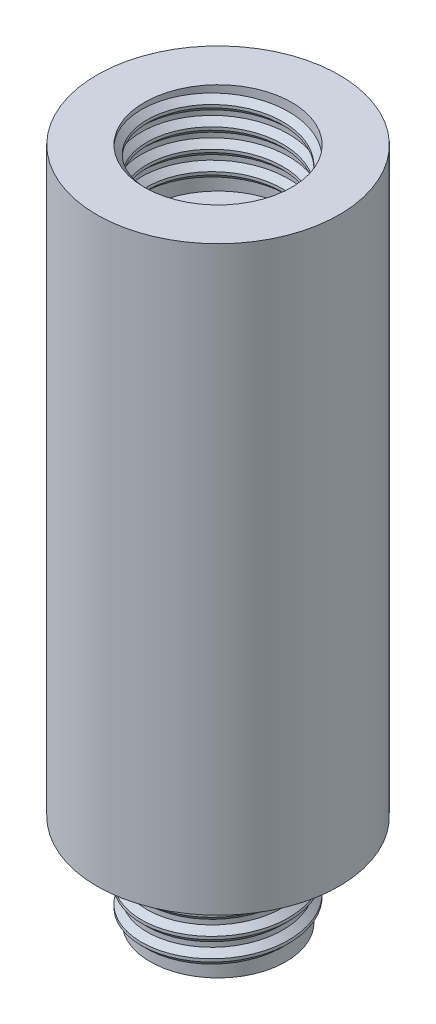
SolidWorks part; units mm, degrees
material "可锻铸铁"
ref_plane "前视基准面" through (0, 0, 0) normal (0, 0, 1) x (1, 0, 0)
ref_plane "上视基准面" through (0, 0, 0) normal (0, 1, 0) x (1, 0, 0)
ref_plane "右视基准面" through (0, 0, 0) normal (1, 0, 0) x (0, 0, -1)
other "Configuration Table"
sketch "草图1" plane through (0, 0, 0) normal (0, 1, 0) x (1, 0, 0)
  circle A0 centre (0, 0) radius 12.5
  dimension "D1" = 25
extrude "凸台-拉伸1" add sketch "草图1" along normal blind 60
sketch "草图14" plane through (0, 60, 0) normal (0, 1, 0) x (1, 0, 0)
  circle A0 centre (0, 0) radius 7.6
  dimension "D1" = 15.2
extrude "切除-拉伸1" cut sketch "草图14" against normal blind 9.5
sketch "草图10" plane through (0, 0, 0) normal (0, -1, 0) x (1, 0, 0)
  circle A0 centre (0, 0) radius 7
  dimension "D1" = 14
extrude "凸台-拉伸2" add sketch "草图10" along normal blind 9.5
ref_plane "基准面3" through (0, -0.75, 0) normal (0, -1, 0) x (-1, 0, 0)
sketch "草图16" plane through (0, -0.75, 0) normal (0, -1, 0) x (-1, 0, 0)
  circle A0 centre (0, 0) radius 7 construction
  circle A1 centre (0, 0) radius 7
curve "螺旋线/涡状线1" pitch 2 height 8 radius 7 centre (0, -0.75, 0) axis (0, -1, 0) start towards (0, 0, -1)
sketch "草图17" plane through (0, 0, 0) normal (1, 0, 0) x (0, 0, -1)
  line L0 (7, 0) -> (7, -1.5)
  line L1 (7, -1.5) -> (7.6, -0.9)
  line L2 (7.6, -0.9) -> (7.6, -0.6)
  line L3 (7.6, -0.6) -> (7, 0)
  point P2 (7, -0.75)
  dimension "D1" = 1.5
  dimension "D2" = 45
  dimension "D3" = 45
  dimension "D4" = 0.6
sweep "扫描1" add profiles "草图17" path "螺旋线/涡状线1"
ref_plane "基准面4" through (0, 59.25, 0) normal (0, 1, 0) x (1, 0, 0)
sketch "草图18" plane through (0, 59.25, 0) normal (0, 1, 0) x (1, 0, 0)
  circle A2 centre (0, 0) radius 7.6 construction
  circle A3 centre (0, 0) radius 7.6
curve "螺旋线/涡状线2" pitch 2 height 8 radius 7.6 centre (0, 59.25, 0) axis (0, -1, 0) start towards (0, 0, 1)
sketch "草图19" plane through (0, 0, 0) normal (1, 0, 0) x (0, 0, -1)
  line L0 (-7.6, 52) -> (-7.6, 50.5)
  line L1 (-7.6, 50.5) -> (-7, 51.1)
  line L2 (-7, 51.1) -> (-7, 51.4)
  line L3 (-7, 51.4) -> (-7.6, 52)
  point P2 (-7.6, 51.25)
  dimension "D1" = 1.5
  dimension "D2" = 0.6
  dimension "D3" = 45
  dimension "D4" = 45
sweep "扫描2" add profiles "草图19" path "螺旋线/涡状线2"
